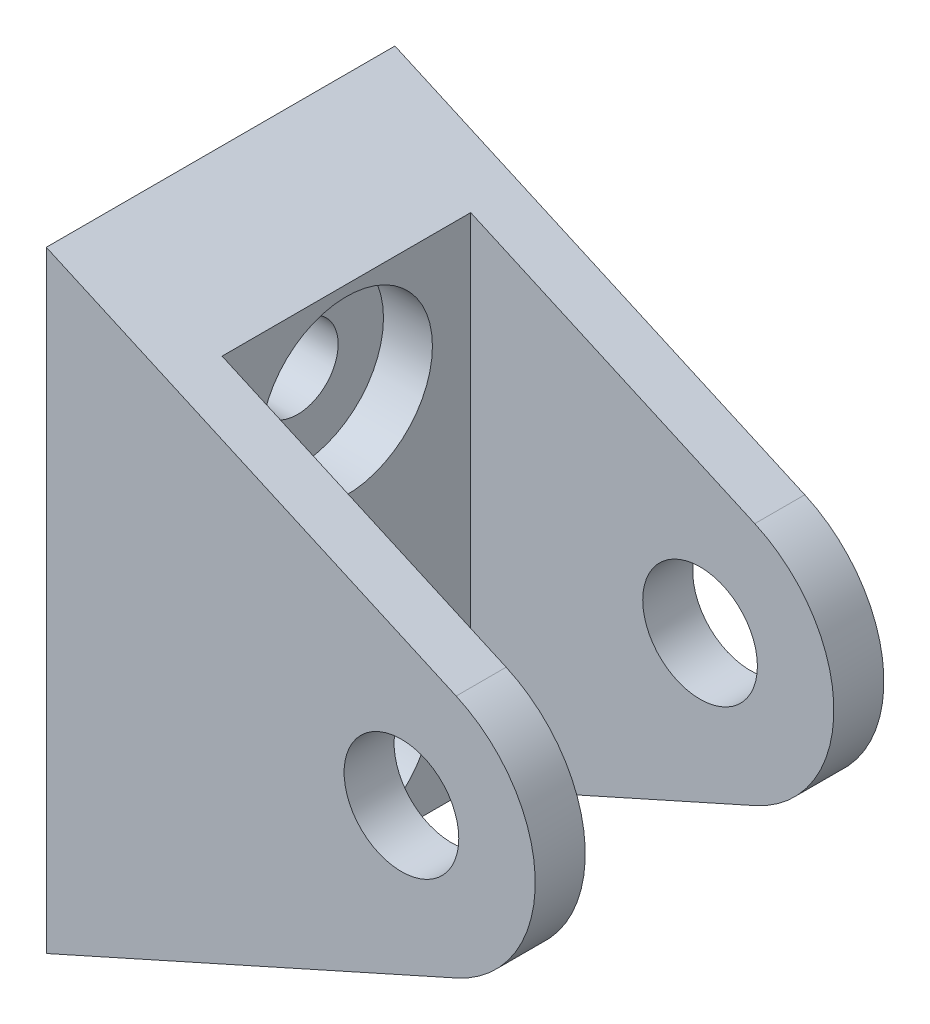
SolidWorks part; units mm, degrees
material "6061-T6 (SS)"
ref_plane "Front Plane" through (0, 0, 0) normal (0, 0, 1) x (1, 0, 0)
ref_plane "Top Plane" through (0, 0, 0) normal (0, 1, 0) x (1, 0, 0)
ref_plane "Right Plane" through (0, 0, 0) normal (1, 0, 0) x (0, 0, -1)
sketch "Sketch1" plane through (0, 0, 0) normal (0, 1, 0) x (1, 0, 0)
  line L0 (0, 0) -> (42.1978, 0)
  line L1 (42.1978, 0) -> (42.1978, 4.1529)
  line L2 (42.1978, 4.1529) -> (10.4478, 4.1529)
  line L3 (10.4478, 4.1529) -> (10.4478, 24.8031)
  line L4 (10.4478, 24.8031) -> (42.1978, 24.8031)
  line L5 (42.1978, 24.8031) -> (42.1978, 28.956)
  line L6 (42.1978, 28.956) -> (0, 28.956)
  line L7 (0, 28.956) -> (0, 0)
  line L8 (29.4978, 28.956) -> (29.4978, 0) construction
  circle A0 centre (29.4978, 14.478) radius 10.3505 construction
  dimension "D4" = 20.701
  dimension "D1" = 28.956
  dimension "D2" = 31.75
  dimension "D3" = 20.6502
  dimension "D5" = 12.7
extrude "Camber Block Extrude" add sketch "Sketch1" along normal blind 50.8
sketch "Sketch2" plane through (10.4478, 0, 0) normal (1, 0, 0) x (0, 0, -1)
  line L0 (4.1529, 25.4) -> (24.8031, 25.4) construction
  line L1 (4.1529, 50.8) -> (4.1529, 0) construction
  line L2 (24.8031, 50.8) -> (24.8031, 0) construction
  line L3 (14.478, 38.1) -> (14.478, 12.7) construction
  circle A0 centre (14.478, 38.1) radius 3.175 construction
  circle A1 centre (14.478, 12.7) radius 3.175 construction
  point P6 (14.478, 38.1)
  point P7 (14.478, 12.7)
  point P10 (14.478, 25.4)
  point P12 (14.478, 25.4)
  point P17 (14.478, 38.1)
  point P19 (14.478, 12.7)
  dimension "D2" = 6.35
  dimension "D3" = 6.35
  dimension "D1" = 25.4
hole_wizard "CBORE for 1/4 Binding Head Machine Screw1" positions "Sketch2" profile "Sketch3" counterbore size "1/4" standard "ANSI Inch" end condition through all
sketch "Sketch3" plane through (10.4478, 12.7, -14.478) normal (0, 1, 0) x (0, 0, -1)
  line L0 (0, 0) -> (0, 10.4478)
  line L1 (0, 10.4478) -> (3.3782, 10.4478)
  line L3 (3.3782, 10.4478) -> (3.3782, 4.064)
  line L4 (3.3782, 4.064) -> (7.1437, 4.064)
  line L5 (7.1437, 4.064) -> (7.1437, 0)
  line L7 (7.1437, 0) -> (0, 0)
  line L11 (0, -6.35) -> (0, 107.95) construction
  dimension "Thru Hole Dia." = 6.7564
  dimension "Thru Hole Depth" = 10.4478
  dimension "C'Bore Dia." = 14.2875
  dimension "C'Bore Depth" = 4.064
sketch "Sketch5" plane through (0, 0, 0) normal (0, 0, 1) x (1, 0, 0)
  line L0 (0, 25.4) -> (42.1978, 25.4) construction
  line L1 (0, 50.8) -> (0, 0) construction
  line L2 (42.1978, 50.8) -> (42.1978, 0) construction
  line L3 (0, 0) -> (34.0431, 15.2596)
  line L4 (0, 50.8) -> (34.0431, 35.5404)
  line L5 (0, 0) -> (42.1978, 0)
  line L6 (42.1978, 0) -> (42.1978, 50.8)
  line L7 (42.1978, 50.8) -> (0, 50.8)
  circle A0 centre (29.4978, 25.4) radius 4.7625
  arc A1 (34.0431, 15.2596) -> (34.0431, 35.5404) centre (29.4978, 25.4) ccw
  dimension "D1" = 9.525
  dimension "D2" = 6.35
extrude "Cut-Extrude1" cut sketch "Sketch5" against normal up to surface (28.956 mm away) up to face at (21.0989, 25.4, -28.956)
